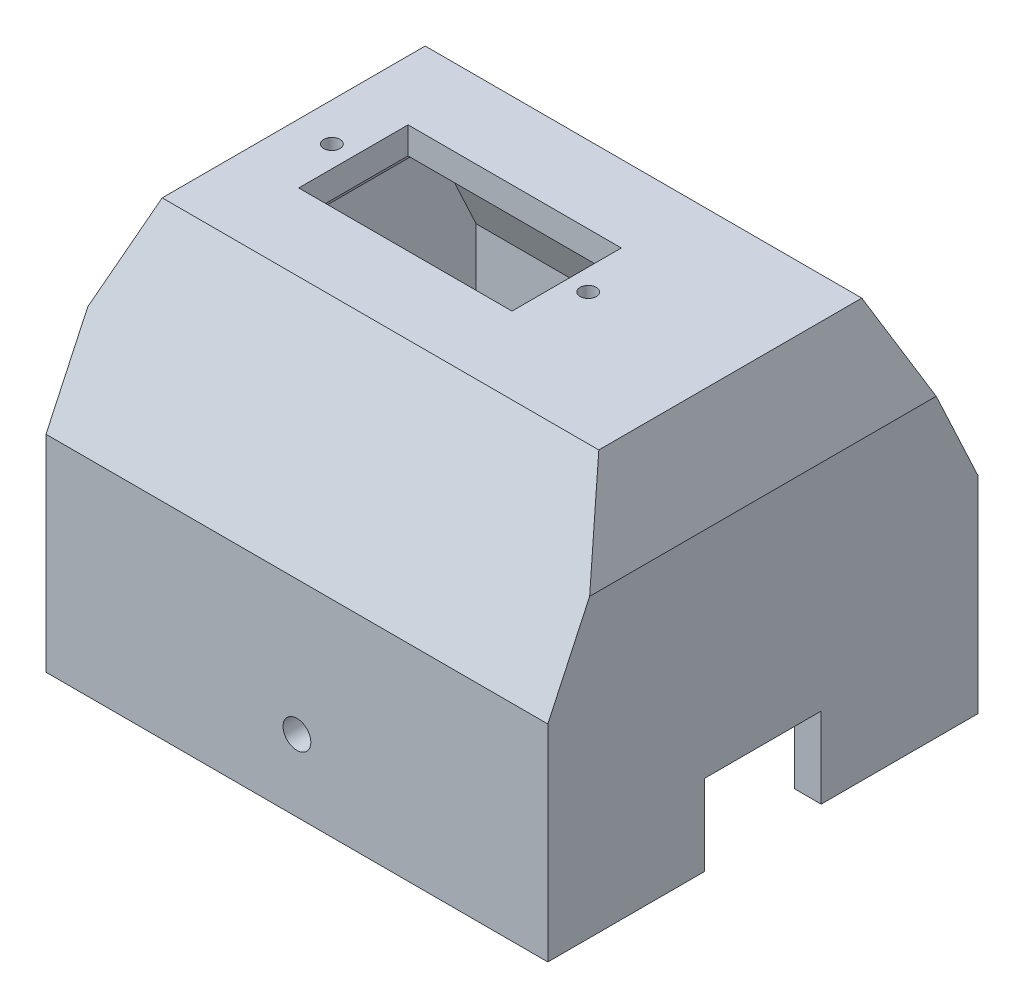
SolidWorks part; units mm, degrees
ref_plane "前视基准面" through (0, 0, 0) normal (0, 0, 1) x (1, 0, 0)
ref_plane "上视基准面" through (0, 0, 0) normal (0, 1, 0) x (1, 0, 0)
ref_plane "右视基准面" through (0, 0, 0) normal (1, 0, 0) x (0, 0, -1)
sketch "草图47" plane through (0, 0, 0) normal (0, 1, 0) x (1, 0, 0)
  line L1 (28, -24) -> (-28, -24)
  line L2 (28, -24) -> (28, 24)
  line L3 (28, 24) -> (-28, 24)
  line L4 (-28, -24) -> (-28, 24)
  line L5 (28, -24) -> (-28, 24) construction
  line L6 (28, 24) -> (-28, -24) construction
  point P0 (0, 0)
  dimension "D1" = 48
  dimension "D2" = 56
extrude "凸台-拉伸4" add sketch "草图47" along normal blind 43
chamfer "倒角1" distance 10 angle 20 2 edges at (28, 43, 0) (-28, 43, 0) first distance on face at (28, 21.5, 0) first distance on face at (-28, 21.5, 0)
chamfer "倒角2" distance 20 angle 25 2 edges at (0, 43, -24) (0, 43, 24) first distance on face at (0, 25.3333, -24) first distance on face at (0, 25.3333, 24)
shell "抽壳1" thickness 3 removed face at (0, 0, 0)
sketch "草图48" plane through (0, 43, -43) normal (0, -1, 0) x (1, 0, 0)
  line L0 (-5.8, 47.679) -> (-5.8, 60.2141) construction
  line L1 (6.1, 36.9) -> (-17.7, 36.9)
  line L2 (6.1, 36.9) -> (6.1, 49.1)
  line L3 (6.1, 49.1) -> (-17.7, 49.1)
  line L4 (-17.7, 36.9) -> (-17.7, 49.1)
  line L5 (6.1, 36.9) -> (-17.7, 49.1) construction
  line L6 (6.1, 49.1) -> (-17.7, 36.9) construction
  line L13 (-20.1, 43) -> (-5.8, 43) construction
  circle A0 centre (-20.1, 43) radius 0.9
  circle A2 centre (8.5, 43) radius 0.9
  circle A3 centre (0, 43) radius 6.1 construction
  point P0 (-5.8, 43)
  point P6 (-5.8, 43)
  point P10 (0, 43)
  dimension "D4" = 1.8
  dimension "D1" = 23.8
  dimension "D2" = 12.2
  dimension "D3" = 14.3
extrude "切除-拉伸3" cut sketch "草图48" along normal up to next
sketch "草图49" plane through (0, 0, -24) normal (0, 0, -1) x (-1, 0, 0)
  line L0 (-28, 0) -> (28, 0) construction
  circle A0 centre (0, 8) radius 1.55
  point P4 (0, 0)
  dimension "D1" = 3.1
  dimension "D2" = 8
extrude "切除-拉伸4" cut sketch "草图49" against normal through all
sketch "草图50" plane through (28, 0, 0) normal (1, 0, 0) x (0, 0, -1)
  line L0 (-24, 0) -> (24, 0) construction
  line L1 (6.5, 9) -> (-6.5, 9)
  line L2 (6.5, 9) -> (6.5, 0)
  line L3 (6.5, 0) -> (-6.5, 0)
  line L4 (-6.5, 9) -> (-6.5, 0)
  line L5 (6.5, 9) -> (-6.5, 0) construction
  line L6 (6.5, 0) -> (-6.5, 9) construction
  point P0 (0, 4.5)
  dimension "D1" = 9
  dimension "D2" = 13
extrude "切除-拉伸5" cut sketch "草图50" against normal up to next
sketch "草图51" plane through (-28, 0, 0) normal (-1, 0, 0) x (0, 0, 1)
  line L0 (-24, 0) -> (24, 0) construction
  line L1 (5.3596, 21.8798) -> (-5.3596, 21.8798)
  line L2 (5.3596, 21.8798) -> (5.3596, 0)
  line L3 (5.3596, 0) -> (-5.3596, 0)
  line L4 (-5.3596, 21.8798) -> (-5.3596, 0)
  line L5 (5.3596, 21.8798) -> (-5.3596, 0) construction
  line L6 (5.3596, 0) -> (-5.3596, 21.8798) construction
  point P0 (0, 10.9399)
extrude "切除-拉伸6" cut sketch "草图51" against normal up to next
